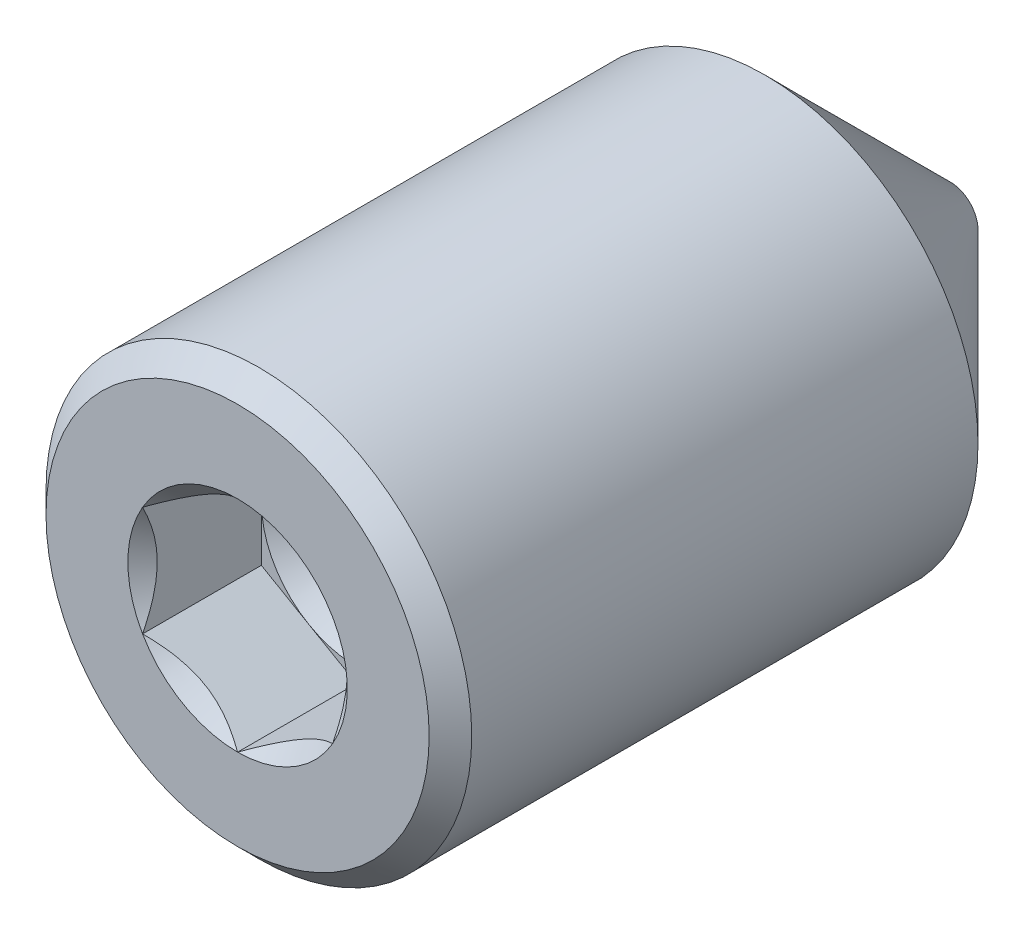
SolidWorks part; units mm, degrees
ref_plane "Front Plane" through (0, 0, 0) normal (0, 0, 1) x (1, 0, 0)
ref_plane "Top Plane" through (0, 0, 0) normal (0, 1, 0) x (1, 0, 0)
ref_plane "Right Plane" through (0, 0, 0) normal (1, 0, 0) x (0, 0, -1)
sketch "Sketch1" plane through (0, 0, 0) normal (1, 0, 0) x (0, 0, -1)
  line L0 (2.3529, 1.4714) -> (2.5794, 1.0791) construction
  line L1 (-2.3812, 1.4224) -> (2.3812, 1.4224) construction
  line L2 (-2.3812, 1.4224) -> (-2.3812, -1.4224) construction
  line L3 (-2.3812, -1.4224) -> (2.3812, -1.4224) construction
  line L4 (2.3812, 1.4224) -> (2.3812, -1.4224) construction
  line L5 (0, -1.4224) -> (0, 1.4224) construction
  line L6 (-2.3812, 0) -> (2.3812, 0) construction
  line L7 (2.5794, 1.0791) -> (2.8059, 1.4714) construction
  line L8 (2.8059, 1.4714) -> (2.3529, 1.4714) construction
  line L9 (2.5794, 1.4714) -> (2.5794, 1.4224) construction
  line L10 (2.5794, 1.4224) -> (2.5794, 1.1282) construction
  line L11 (2.5794, 1.1282) -> (2.5794, 1.0791) construction
  line L12 (2.5794, 1.4469) -> (2.7918, 1.4469) construction
  line L13 (2.5794, 1.4469) -> (2.3671, 1.4469) construction
  line L14 (2.3812, 1.4224) -> (2.7776, 1.4224) construction
  line L15 (2.5511, 1.1282) -> (2.6078, 1.1282) construction
  line L20 (2.3812, 0.1849) -> (1.1438, 1.4224) construction
  line L21 (2.3812, 0.1849) -> (2.1963, 0) construction
  line L22 (2.1963, 0) -> (2.3812, -0.1849) construction
  line L23 (2.3812, -0.1849) -> (1.1438, -1.4224) construction
  line L24 (1.1438, -1.4224) -> (1.1438, 1.4224) construction
  point P0 (0, 0)
  point P2 (2.9398, 0.3737)
  point P20 (2.3812, 0.1849)
  point P21 (-2.3812, -0.635)
  point P25 (0.5632, -1.4224)
  point P26 (2.3812, -0.1849)
  dimension "Length" = 4.7625
  dimension "Screw Size Decimal Equivalent" = 2.8448
  dimension "Thread Pitch" = 0.453
  dimension "D2" = 0.0566
  dimension "Point" = 0.3698
  dimension "Cone Point Angle" = 90
  dimension "Drive Size" = 1.27
  dimension "D3" = 90
  dimension "D1" = 2.9445
  dimension "D4" = 2.54
sketch "Sketch2" plane through (0, 0, 0) normal (1, 0, 0) x (0, 0, -1)
  line L0 (-2.3812, 0) -> (2.3812, 0)
  line L1 (2.3812, 0) -> (2.3812, 0.1849)
  line L2 (2.3812, 0.1849) -> (1.1438, 1.4224)
  line L3 (1.1438, 1.4224) -> (-2.3812, 1.4224)
  line L4 (-2.3812, 1.4224) -> (-2.3812, 0)
revolve "Revolve1" add sketch "Sketch2" angle 360 about L6
chamfer "Chamfer1" distance 0.1422 angle 45 1 edges at (1.4224, 0, 2.3812)
sketch "Sketch3" plane through (0, 0, 2.3812) normal (0, 0, 1) x (1, 0, 0)
  line L1 (0, -0.7332) -> (0.635, -0.3666)
  line L2 (0.635, -0.3666) -> (0.635, 0.3666)
  line L3 (0.635, 0.3666) -> (0, 0.7332)
  line L4 (0, 0.7332) -> (-0.635, 0.3666)
  line L5 (-0.635, 0.3666) -> (-0.635, -0.3666)
  line L6 (-0.635, -0.3666) -> (0, -0.7332)
  circle A0 centre (0, 0) radius 0.635 construction
  dimension "D1" = 1.27
extrude "Cut-Extrude1" cut sketch "Sketch3" against normal blind 0.7937
sketch "Sketch4" plane through (0, 0, 2.3812) normal (0, 0, 1) x (1, 0, 0)
  circle A0 centre (0, 0) radius 0.7332
extrude "Cut-Extrude2" cut sketch "Sketch4" against normal through all draft 45
sketch "Sketch5" plane through (0, 0, 1.5875) normal (0, 0, 1) x (1, 0, 0)
  line L0 (0, 0.7332) -> (0.635, 0.3666) construction
  circle A0 centre (0, 0) radius 0.635
extrude "Cut-Extrude3" cut sketch "Sketch5" against normal through all draft 45
sketch "Sketch6" [suppressed] plane through (0, 0, -2.3812) normal (0, 0, -1) x (-1, 0, 0)
  circle A0 centre (0, 0) radius 1.4224 construction
  circle A1 centre (0, 0) radius 1.4224
curve "Helix/Spiral1" [suppressed] pitch 0.453 height 5.2155 turns 11.5132
sketch "Sketch7" [suppressed] plane through (0, 0, 0) normal (1, 0, 0) x (0, 0, -1)
  line L0 (2.3671, 1.4469) -> (2.7918, 1.4469)
  line L1 (2.7918, 1.4469) -> (2.6078, 1.1282)
  line L2 (2.6078, 1.1282) -> (2.5511, 1.1282)
  line L3 (2.5511, 1.1282) -> (2.3671, 1.4469)
sweep "Cut-Sweep1" [suppressed] cut profiles "Sketch7" path "Helix/Spiral1"
equation "\"D2@Sketch1\" = \"Thread Pitch@Sketch1\" / 8"
equation "\"Point@Sketch1\"=\"Screw Size Decimal Equivalent@Sketch1\"*.13"
equation "\"D1@Chamfer1\"=\"Screw Size Decimal Equivalent@Sketch1\"*.05"
equation "\"D1@Sketch3\"=\"Drive Size@Sketch1\""
equation "\"D1@Cut-Extrude1\"=\"Drive Size@Sketch1\"*.625"
equation "\"D4@Helix/Spiral1\"=\"Thread Pitch@Sketch1\""
equation "\"D3@Helix/Spiral1\"=\"Length@Sketch1\"+\"Thread Pitch@Sketch1\""
equation "\"D3@Sketch1\"=\"Cone Point Angle@Sketch1\""
equation "\"D1@Sketch1\"=\"Thread Pitch@Sketch1\"*6.5"
